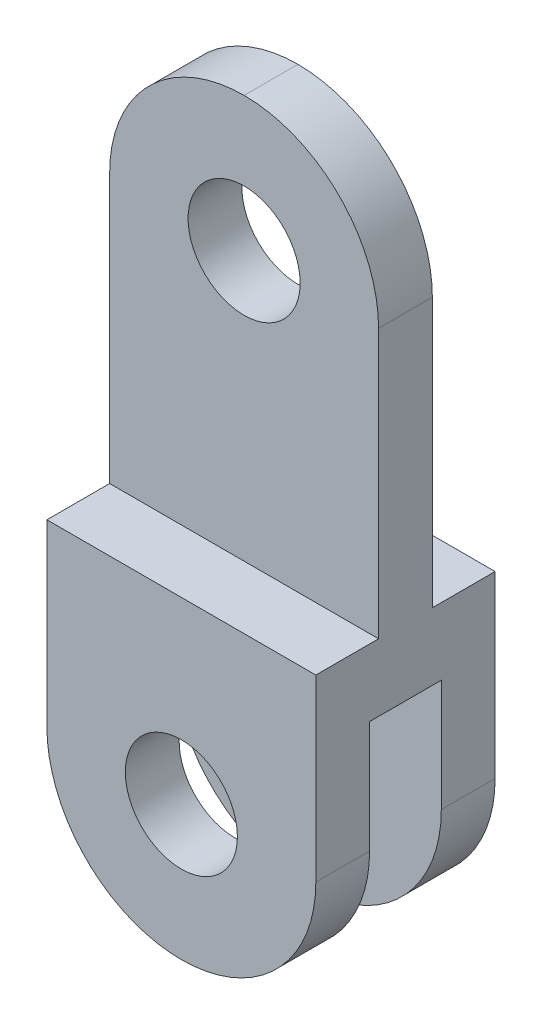
SolidWorks part; units mm, degrees
ref_plane "Front Plane" through (0, 0, 0) normal (1, 0, 0) x (0, 1, 0)
ref_plane "Top Plane" through (0, 0, 0) normal (0, 0, 1) x (0, 1, 0)
ref_plane "Right Plane" through (0, 0, 0) normal (0, 1, 0) x (-1, 0, 0)
sketch "Sketch1" plane through (0, 0, 0) normal (1, 0, 0) x (0, 1, 0)
  line L0 (0, 0) -> (29672.009, 0) construction
  line L1 (0, 0) -> (0, 29672.009) construction
  line L2 (0, -8) -> (0, 8)
  line L3 (0, 8) -> (-55, 8)
  line L4 (-55, 8) -> (-55, 20)
  line L5 (-55, 20) -> (15, 20)
  line L6 (15, 20) -> (15, 6)
  line L7 (15, 6) -> (105, 6)
  line L8 (105, 6) -> (105, -6)
  line L9 (15, -6) -> (105, -6)
  line L10 (15, -20) -> (15, -6)
  line L11 (-55, -20) -> (15, -20)
  line L12 (0, -8) -> (-55, -8)
  line L13 (-55, -8) -> (-55, -20)
  line L14 (-25, 44.5335) -> (-25, -31.5051) construction
  line L15 (75, 41.5092) -> (75, -30.009) construction
  point P14 (105, 0)
  point P16 (0, 0)
  dimension "D1" = 40
  dimension "D2" = 12
  dimension "D3" = 15
  dimension "D4" = 30
  dimension "D5" = 30
  dimension "D6" = 100
  dimension "D7" = 25
  dimension "D8" = 12
extrude "Boss-Extrude1" add sketch "Sketch1" along normal mid plane 60
fillet "Fillet1" radius 30 6 edges at (-30, 105, 0) (30, 105, 0) (30, -55, -14) (-30, -55, -14) (-30, -55, 14) (30, -55, 14)
sketch "Sketch3" plane through (0, 0, 20) normal (0, 0, 1) x (1, 0, 0)
  circle A0 centre (0, -25) radius 12.5
  arc A1 (0, -55) -> (30, -25) centre (0, -25) ccw construction
  circle A2 centre (0, 75) radius 12.5
  arc A3 (30, 75) -> (0, 105) centre (0, 75) ccw construction
  dimension "D1" = 25
  dimension "D2" = 25
extrude "Cut-Extrude1" cut sketch "Sketch3" against normal through all both and the other way through all
